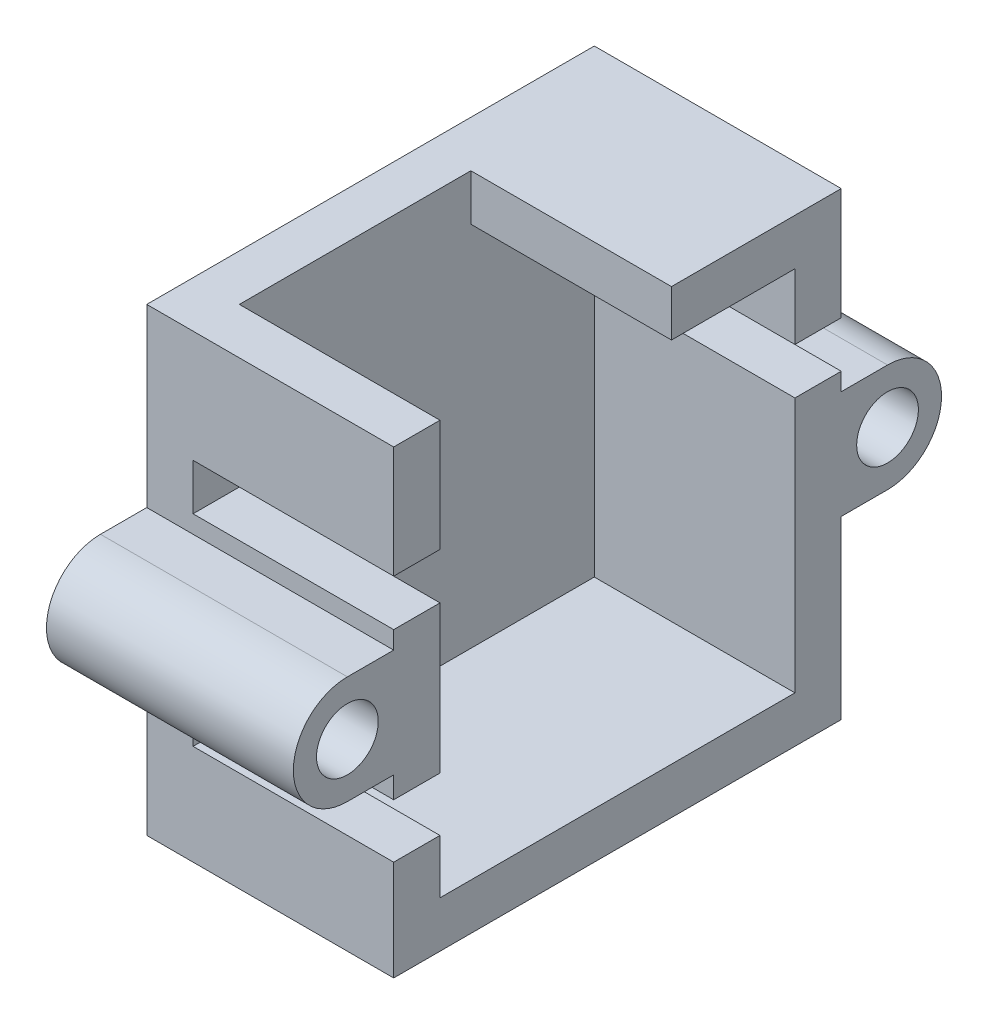
SolidWorks part; units mm, degrees
ref_plane "Front Plane" through (0, 0, 0) normal (0, 0, 1) x (1, 0, 0)
ref_plane "Top Plane" through (0, 0, 0) normal (0, 1, 0) x (1, 0, 0)
ref_plane "Right Plane" through (0, 0, 0) normal (1, 0, 0) x (0, 0, -1)
sketch "Sketch1" plane through (0, 0, 0) normal (1, 0, 0) x (0, 0, -1)
  line L0 (-3, -3) -> (-3, 26.8)
  line L1 (0, 0) -> (23, 0)
  line L2 (0, 0) -> (0, 23.8)
  line L3 (0, 23.8) -> (23, 23.8)
  line L4 (23, 0) -> (23, 23.8)
  line L5 (-3, 26.8) -> (26, 26.8)
  line L6 (26, -3) -> (26, 26.8)
  line L7 (-3, -3) -> (26, -3)
  dimension "D1" = 23.8
  dimension "D2" = 23
  dimension "D3" = 3
extrude "sides" add sketch "Sketch1" along normal blind 13
sketch "Sketch2" plane through (0, 0, 0) normal (1, 0, 0) x (0, 0, -1)
  line L0 (-3, 26.8) -> (-3, -3) construction
  line L1 (-3, -3) -> (26, -3) construction
  line L2 (26, -3) -> (26, 26.8) construction
  line L3 (26, 26.8) -> (-3, 26.8) construction
  line L4 (-3, 26.8) -> (-3, -3)
  line L5 (-3, -3) -> (26, -3)
  line L6 (26, -3) -> (26, 26.8)
  line L7 (26, 26.8) -> (-3, 26.8)
extrude "base" add sketch "Sketch2" against normal blind 3
sketch "Sketch3" plane through (0, 0, 0) normal (1, 0, 0) x (0, 0, -1)
  line L1 (-3, 19.55) -> (26, 19.55)
  line L2 (-3, 19.55) -> (-3, 16.55)
  line L3 (-3, 16.55) -> (26, 16.55)
  line L4 (26, 19.55) -> (26, 16.55)
  line L5 (26, -3) -> (26, 26.8) construction
  line L6 (23, 23.8) -> (0, 23.8) construction
  line L7 (-3, 26.8) -> (-3, -3) construction
  dimension "D1" = 4.25
  dimension "D2" = 3
extrude "servo wing slots" cut sketch "Sketch3" along normal up to surface (13 mm away) up to face at (13, 11.9, -11.5)
sketch "Sketch4" plane through (0, 0, 0) normal (1, 0, 0) x (0, 0, -1)
  line L0 (-3, 16.55) -> (-3, -3) construction
  line L1 (-3, 3.5) -> (0, 3.5)
  line L2 (-3, 3.5) -> (-3, 7)
  line L3 (-3, 7) -> (0, 7)
  line L4 (0, 3.5) -> (0, 7)
  line L5 (0, 16.55) -> (0, 0) construction
  line L6 (0, 0) -> (23, 0) construction
  dimension "D1" = 3.5
  dimension "D2" = 3.5
extrude "servo wire slot" cut sketch "Sketch4" along normal up to surface (13 mm away) up to face at (13, 7.525, -11.5)
sketch "Sketch5" plane through (0, 0, 0) normal (1, 0, 0) x (0, 0, -1)
  line L0 (26, 26.8) -> (-3, 26.8) construction
  line L1 (0, 23.8) -> (15, 23.8)
  line L2 (0, 23.8) -> (0, 26.8)
  line L3 (0, 26.8) -> (15, 26.8)
  line L4 (15, 23.8) -> (15, 26.8)
  dimension "D1" = 15
extrude "servo head opening" cut sketch "Sketch5" along normal up to surface (13 mm away) up to face at (13, 22.425, -11.5)
sketch "Sketch6" plane through (0, 0, 0) normal (1, 0, 0) x (0, 0, -1)
  line L0 (-3, 26.8) -> (-3, -3) construction
  line L1 (-3, 26.8) -> (-3, -3) construction
  line L2 (-3, 11.9) -> (26, 11.9) construction
  line L3 (26, -3) -> (26, 16.55) construction
  line L4 (-6, 15.4) -> (-3, 15.4)
  line L5 (-3, 15.4) -> (-3, 8.4)
  line L6 (-3, 8.4) -> (-6, 8.4)
  line L7 (11.5, -3) -> (11.5, 26.8) construction
  line L8 (15, 26.8) -> (0, 26.8) construction
  line L9 (29, 15.4) -> (26, 15.4)
  line L10 (26, 15.4) -> (26, 8.4)
  line L11 (26, 8.4) -> (29, 8.4)
  arc A0 (-6, 15.4) -> (-6, 8.4) centre (-6, 11.9) ccw
  circle A1 centre (-6, 11.9) radius 2
  circle A2 centre (29, 11.9) radius 2
  arc A3 (29, 15.4) -> (29, 8.4) centre (29, 11.9) cw
  point P17 (11.5, 11.9)
  dimension "D2" = 7
  dimension "D3" = 4
  dimension "D1" = 3
extrude "mount" add sketch "Sketch6" along normal up to surface and the other way up to surface contours A0 L6 L5 L4 | L9 L10 L11 A3 | A1 | A2 up to face at (13, 11.775, 1.5) other way up to face at (-3, 11.9, -11.5)
sketch "Sketch7" [suppressed] plane through (0, 0, 0) normal (1, 0, 0) x (0, 0, -1)
  line L0 (-3, -3) -> (26, -3) construction
  line L1 (-8.75, 26) -> (31.75, 26)
  line L2 (-8.75, 26) -> (-8.75, -3)
  line L3 (-8.75, -3) -> (31.75, -3)
  line L4 (31.75, 26) -> (31.75, -3)
  line L5 (15, 26) -> (0, 26) construction
  arc A0 (-6, 14.25) -> (-6, 8.75) centre (-6, 11.5) ccw construction
  arc A1 (29, 8.75) -> (29, 14.25) centre (29, 11.5) ccw construction
extrude "lid cut" [suppressed] cut sketch "Sketch7" along normal up to surface (13 mm away)
sketch "Sketch9" [suppressed] plane through (0, -3, 0) normal (0, -1, 0) x (1, 0, 0)
  line L0 (13, 3) -> (-3, 3) construction
  line L1 (13, 3) -> (13, -26) construction
  circle A0 centre (6, -6.1) radius 2.05
  dimension "D1" = 4.1
  dimension "D2" = 9.1
  dimension "D3" = 6.65
extrude "aligned dummy axle" [suppressed] add sketch "Sketch9" along normal blind 4.5
ref_axis "dummy axle axis" [suppressed] through (6, -7.5, -6.1) along (0, 1, 0)
